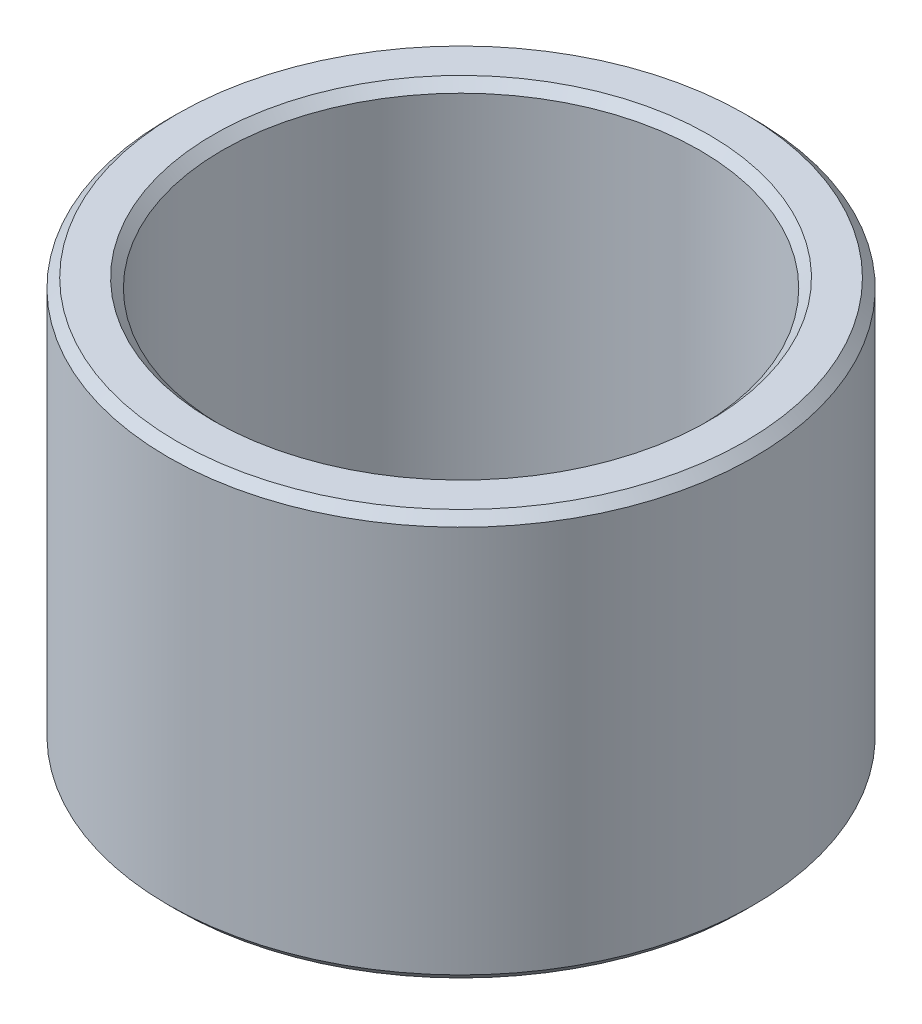
SolidWorks part; units mm, degrees
ref_plane "Front Plane" through (0, 0, 0) normal (0, 0, 1) x (1, 0, 0)
ref_plane "Top Plane" through (0, 0, 0) normal (0, 1, 0) x (1, 0, 0)
ref_plane "Right Plane" through (0, 0, 0) normal (1, 0, 0) x (0, 0, -1)
sketch "Sketch1" plane through (0, 0, 0) normal (0, 1, 0) x (1, 0, 0)
  circle A0 centre (0, 0) radius 40
  dimension "SLEEVE_OD" = 80
extrude "Boss-Extrude1" add sketch "Sketch1" along normal blind 55.4194
sketch "Sketch2" plane through (0, 0, 0) normal (0, 1, 0) x (1, 0, 0)
  circle A0 centre (0, 0) radius 32.6166
  dimension "BORE_D" = 65.2331
extrude "Cut-Extrude1" cut sketch "Sketch2" along normal through all
chamfer "Chamfer1" distance 1.2317 angle 45 4 edges at (0, 55.4194, 32.6166) (0, 0, 32.6166) (0, 0, 40) (0, 55.4194, 40)
